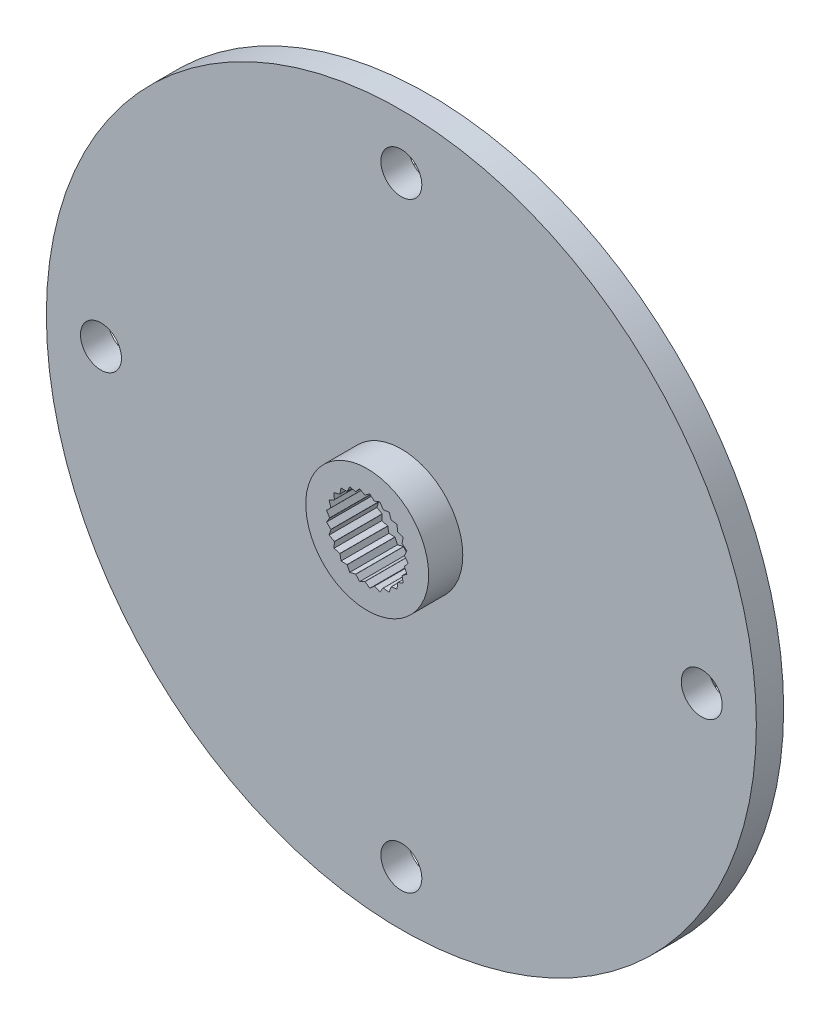
SolidWorks part; units mm, degrees
ref_plane "Front Plane" through (0, 0, 0) normal (0, 0, 1) x (1, 0, 0)
ref_plane "Top Plane" through (0, 0, 0) normal (0, 1, 0) x (1, 0, 0)
ref_plane "Right Plane" through (0, 0, 0) normal (1, 0, 0) x (0, 0, -1)
sketch "Sketch1" plane through (0, 0, 0) normal (0, 0, 1) x (1, 0, 0)
  circle A0 centre (0, 0) radius 26
  circle A1 centre (0, 0) radius 22 construction
  circle A2 centre (0, 22) radius 1.5
  circle A3 centre (22, 0) radius 1.5
  circle A4 centre (0, -22) radius 1.5
  circle A5 centre (-22, 0) radius 1.5
  circle A6 centre (0, 0) radius 4.5
  circle A7 centre (0, 0) radius 18.5 construction
  dimension "D1" = 52
  dimension "D2" = 3
  dimension "D4" = 37
  dimension "D5" = 3.5
  dimension "D3" = 4
extrude "Boss-Extrude1" add sketch "Sketch1" along normal blind 2
extrude "Boss-Extrude2" add sketch "Sketch1<2>" along normal blind 4.5 contours A6 region at (0, 0, 0)
sketch "Sketch1<2>" plane through (0, 0, 0) normal (0, 0, 1) x (1, 0, 0) same geometry as "Sketch1"
sketch "Sketch2" plane through (0, 0, 0) normal (0, 0, -1) x (-1, 0, 0)
  circle A0 centre (0, 0) radius 1.5
extrude "Cut-Extrude1" cut sketch "Sketch2" against normal blind 4.5
sketch "Sketch3" plane through (0, 0, 4.5) normal (0, 0, 1) x (1, 0, 0)
  circle A0 centre (0, 0) radius 2.75
extrude "Cut-Extrude2" cut sketch "Sketch3" against normal blind 3.5
sketch "Sketch4" plane through (0, 0, 4.5) normal (0, 0, 1) x (1, 0, 0)
  line L0 (0, 0) -> (-3, 0)
  line L1 (0, 0) -> (-2.9763, 0.376)
  line L2 (0, 0) -> (-2.9083, 0.7359)
  line L3 (-2.75, 0) -> (-2.9763, 0.376)
  line L4 (-2.666, 0.6746) -> (-2.9763, 0.376)
  circle A0 centre (0, 0) radius 3
  circle A1 centre (0, 0) radius 2.75 construction
  circle A2 centre (0, 0) radius 2.75 construction
  circle A3 centre (0, 0) radius 2.75
  circle M6 centre (0, 0) radius 2.75
  dimension "D1" = 7.2
  dimension "D2" = 14.2
extrude "Cut-Extrude3" cut sketch "Sketch4" against normal blind 3.5 contours L4 L1 M6 | L3 L1 M6 region at (-2.8205, 0.2422, 4.5) region at (-2.7928, 0.4638, 4.5)
pattern_circular "CirPattern1" count 25 over 360 about axis through (0, 0, 4.5) along (0, 0, -1) of "Cut-Extrude3" reverse direction yes
sketch "Sketch5" plane through (0, 0, 0) normal (0, 0, -1) x (-1, 0, 0)
  circle A0 centre (0, 0) radius 18.5
  circle A1 centre (0, 0) radius 1.5
  circle A2 centre (0, 0) radius 1.5 construction
  dimension "11" = 37
extrude "Boss-Extrude3" add sketch "Sketch5" along normal blind 3
ref_plane "Plane1" through (0.0348, -0.0732, -7.5725) normal (-0.0046, 0.0097, 0.9999) x (0.4291, -0.9032, 0.0107)
